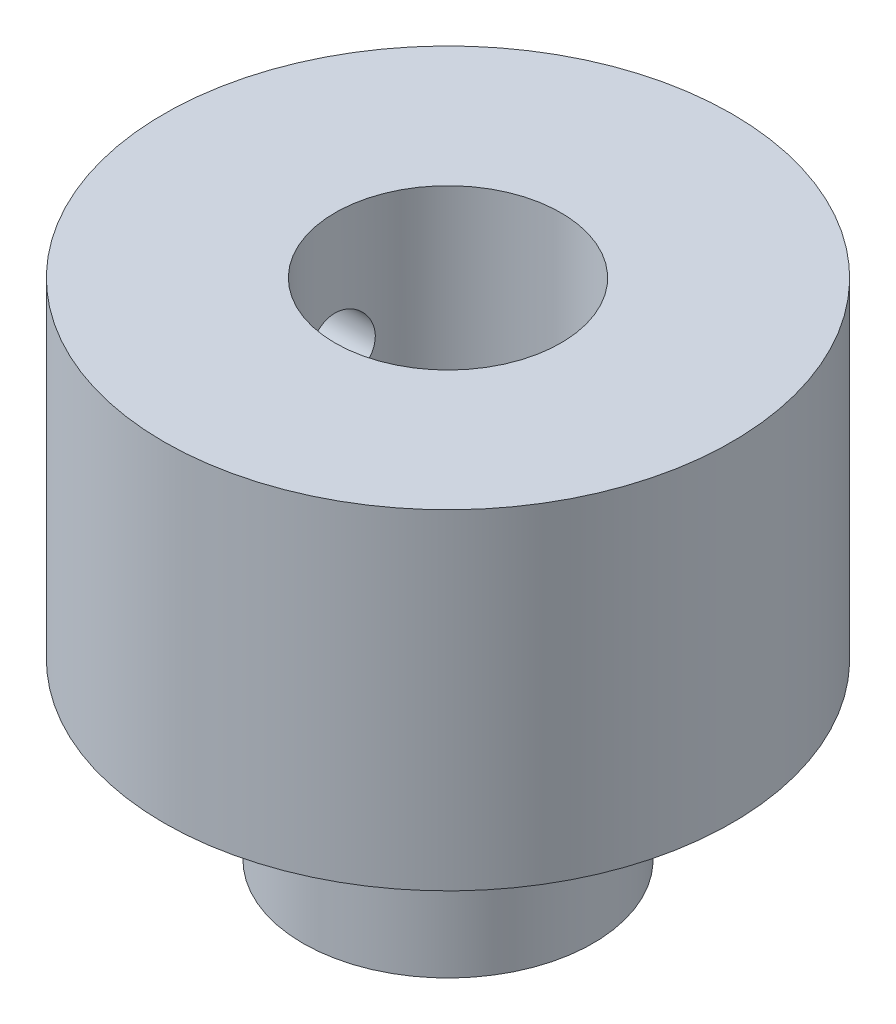
SolidWorks part; units mm, degrees
ref_plane "Front Plane" through (0, 0, 0) normal (0, 0, 1) x (1, 0, 0)
ref_plane "Top Plane" through (0, 0, 0) normal (0, 1, 0) x (1, 0, 0)
ref_plane "Right Plane" through (0, 0, 0) normal (1, 0, 0) x (0, 0, -1)
sketch "Sketch1" plane through (0, 0, 0) normal (0, 1, 0) x (1, 0, 0)
  circle A0 centre (0, 0) radius 3.25
  circle A1 centre (0, 0) radius 8.175
  circle A2 centre (0, 0) radius 8.175
  point P25 (0, 0)
extrude "Boss-Extrude1" add sketch "Sketch1" along normal blind 6.5 and the other way blind 3 contours A1 A0 region at (-7.9438, 0, 0)
extrude "Boss-Extrude2" add sketch "Sketch1<3>" against normal blind 3 separate body contours A2 A1 region at (-7.9438, 0, 0)
sketch "Sketch1<3>" plane through (0, 0, 0) normal (0, 1, 0) x (1, 0, 0) same geometry as "Sketch1"
sketch "Sketch2" plane through (0, 0, 0) normal (1, 0, 0) x (0, 0, -1)
  line L0 (0, 2) -> (0, 0)
  circle A0 centre (0, 3) radius 1
  dimension "D1" = 2
  dimension "D3" = 2
  dimension "D2" = 2
extrude "Cut-Extrude1" cut sketch "Sketch2" against normal blind 15 contours A0
sketch "Sketch3" plane through (0, -3, 0) normal (0, -1, 0) x (1, 0, 0)
  circle A1 centre (0, 11.7973) radius 1
  circle A2 centre (9.2235, 7.3555) radius 1
  circle A3 centre (11.5015, -2.6252) radius 1
  circle A4 centre (5.1187, -10.629) radius 1
  circle A5 centre (-5.1187, -10.629) radius 1
  circle A6 centre (-11.5015, -2.6252) radius 1
  circle A7 centre (-9.2235, 7.3555) radius 1
  point P2 (-12.4894, 10.1484)
  point P3 (0, 0)
  point P14 (0, 0)
  point P18 (0, 11.7973)
  dimension "D1" = 7
extrude "Cut-Extrude2" [suppressed] cut sketch "Sketch3" against normal through all and the other way blind 3.175
sketch "Sketch4" plane through (0, -3, 0) normal (0, -1, 0) x (1, 0, 0)
  circle A0 centre (0, 0) radius 4.175
extrude "Boss-Extrude4" add sketch "Sketch4" along normal blind 5 contours A0
extrude "Cut-Extrude3" cut sketch "Sketch1<5>" against normal blind 13 and the other way blind 15 contours A0
sketch "Sketch1<5>" plane through (0, 0, 0) normal (0, 1, 0) x (1, 0, 0) same geometry as "Sketch1"
